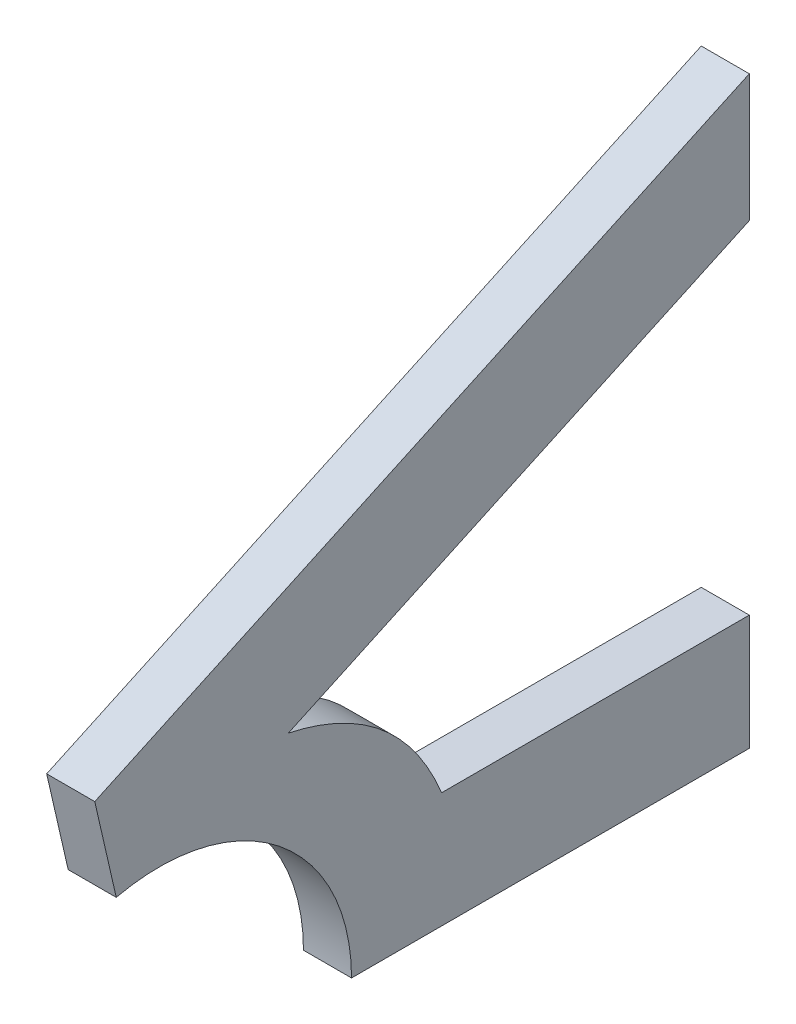
SolidWorks part; units mm, degrees
ref_plane "Front Plane" through (0, 0, 0) normal (0, 0, 1) x (1, 0, 0)
ref_plane "Top Plane" through (0, 0, 0) normal (0, 1, 0) x (1, 0, 0)
ref_plane "Right Plane" through (0, 0, 0) normal (1, 0, 0) x (0, 0, -1)
sketch "Sketch2" plane through (-112.555, 0, -573.5897) normal (-1, 0, 0) x (0, 0.6231, 0.7821)
  line L0 (843.7852, 138.5824) -> (864.3306, 122.2137)
  line L1 (871.0899, 172.8543) -> (811.2713, 97.7721) construction
  line L2 (864.3306, 122.2137) -> (884.1965, 122.2137) construction
  line L3 (884.1965, 122.2137) -> (889.163, 126.1705)
  line L4 (848.5334, 144.5422) -> (864.4261, 131.8803)
  line L5 (889.163, 126.1705) -> (867.8254, 168.7568)
  line L6 (877.6186, 132.2008) -> (862.593, 162.1893)
  line L7 (843.7852, 138.5824) -> (848.5334, 144.5422)
  line L8 (862.593, 162.1893) -> (867.8254, 168.7568)
  circle A0 centre (874.2635, 114.3) radius 12.7 construction
  arc A1 (864.3306, 122.2137) -> (884.1965, 122.2137) centre (874.2635, 114.3) cw
  spline S0 degree 2 poles (864.4261, 131.8803) (870.948, 135.5124) (877.6186, 132.2008) knots 0 0 0 1 1 1
  dimension "D1" = 7.62
  dimension "D2" = 7.62
  dimension "D3" = 6.35
  dimension "D4" = 20.32
extrude "Boss-Extrude1" add sketch "Sketch2" along normal blind 3.175 contours L4 S0 L6 L8 L5 L3 A1 L0 L7
